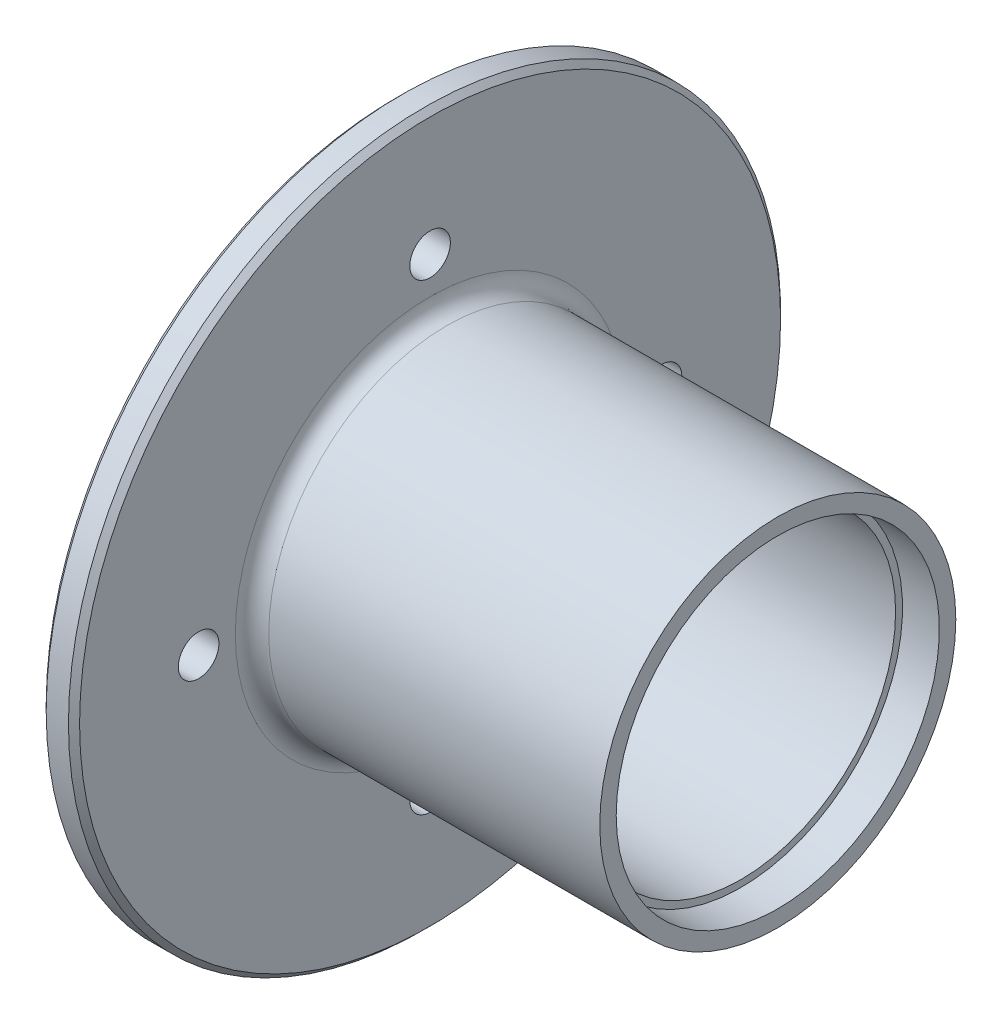
SolidWorks part; units mm, degrees
ref_plane "Plan de face" through (0, 0, 0) normal (0, 0, 1) x (1, 0, 0)
ref_plane "Plan de dessus" through (0, 0, 0) normal (0, 1, 0) x (1, 0, 0)
ref_plane "Plan de droite" through (0, 0, 0) normal (1, 0, 0) x (0, 0, -1)
sketch "Model" plane through (0, 0, 0) normal (0, 0, 1) x (1, 0, 0)
  line L0 (8.1081, 12.547) -> (8.1081, 17.1434)
  line L1 (8.1081, 17.1434) -> (23.5484, 17.1434)
  line L2 (23.5484, 17.1434) -> (23.5484, 22.068)
  line L3 (23.5484, 22.068) -> (52.458, 22.068)
  line L4 (52.458, 22.068) -> (52.458, 23.0529)
  line L6 (57.7143, 23.0529) -> (57.7143, 25.4)
  line L7 (57.7143, 25.4) -> (10.4893, 25.4)
  line L8 (8.1081, 27.7812) -> (8.1081, 50.0062)
  line L9 (7.3143, 50.8) -> (4.1393, 50.8)
  line L10 (3.3456, 50.0062) -> (3.3456, 17.1434)
  line L11 (3.3456, 17.1434) -> (8.1081, 12.547)
  line L12 (8.1081, 50.0062) -> (7.3143, 50.8)
  line L13 (4.1393, 50.8) -> (3.3456, 50.0062)
  line L14 (0, 0) -> (65.0614, 0) construction
  line L42 (52.458, 23.0529) -> (57.7143, 23.0529)
  arc A2 (8.1081, 27.7812) -> (10.4893, 25.4) centre (10.4893, 27.7812) ccw
  point P0 (-207.4989, -142.476)
  dimension "D1" = 2.3813
  dimension "D2" = 3.3456
  dimension "D3" = 4.1393
  dimension "D4" = 7.3143
  dimension "D5" = 12.547
  dimension "D6" = 23.5484
  dimension "D7" = 52.458
  dimension "D8" = 57.7143
  dimension "D9" = 17.1434
  dimension "D10" = 22.068
  dimension "D11" = 23.0529
  dimension "D12" = 25.4
  dimension "D13" = 50.0062
revolve "Révolution1" add sketch "Model" angle 360 about L14 region at (6.1885, 15.3235, 0)
hole_wizard "Dégagement #121" positions "Esquisse3" profile "Esquisse4" hole size "#12" standard "Ansi Inch" end condition through all
sketch "Esquisse3" plane through (8.1081, 0, 0) normal (1, 0, 0) x (0, 0, -1)
  point P0 (0, 33.02)
  dimension "D1" = 33.02
sketch "Esquisse4" plane through (8.1081, 33.02, 0) normal (0, 1, 0) x (0, 0, -1)
  line L0 (0, 0) -> (0, 4.7625)
  line L1 (0, 4.7625) -> (2.8956, 4.7625)
  line L2 (2.8956, 4.7625) -> (2.8956, 0)
  line L5 (2.8956, 0) -> (0, 0)
  line L11 (0, -6.35) -> (0, 107.95) construction
  dimension "Diamètre du perçage jusqu'au prochain" = 5.7912
  dimension "Profondeur du perçage jusqu'au prochain" = 4.7625
ref_axis "Axe1" through (57.7143, 0, 0) along (-1, 0, 0)
pattern_circular "Répétition circulaire1" count 4 over 360 about axis through (57.7143, 0, 0) along (-1, 0, 0) of "Dégagement #121"
